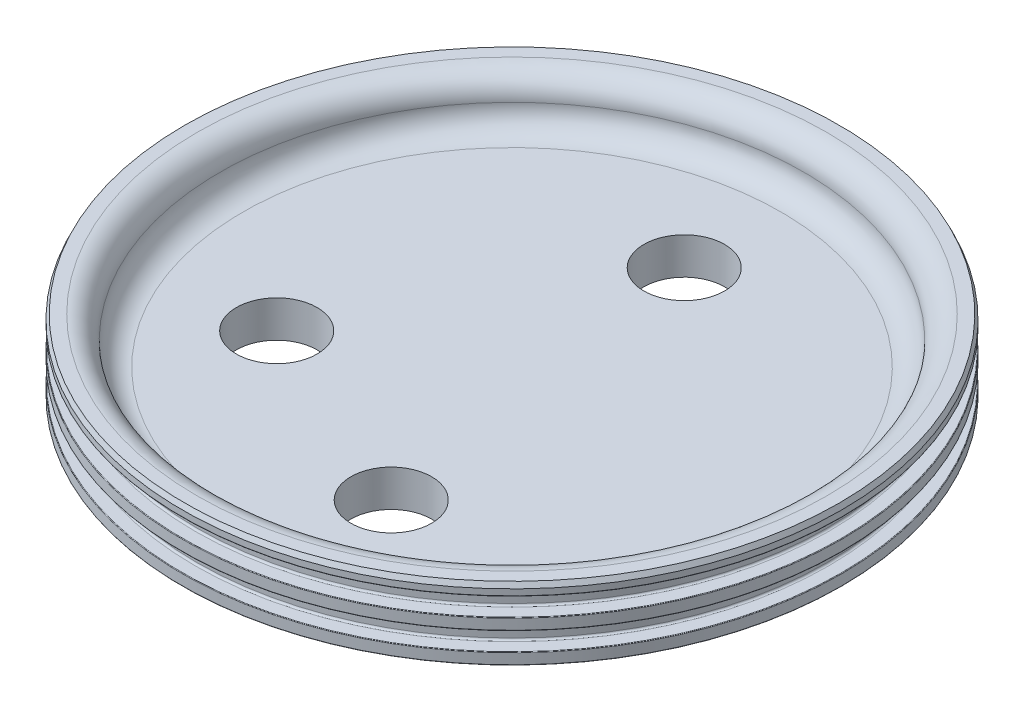
SolidWorks part; units mm, degrees
material "6061-T6 (SS)"
ref_plane "Front Plane" through (0, 0, 0) normal (0, 0, 1) x (1, 0, 0)
ref_plane "Top Plane" through (0, 0, 0) normal (0, 1, 0) x (1, 0, 0)
ref_plane "Right Plane" through (0, 0, 0) normal (1, 0, 0) x (0, 0, -1)
sketch "Sketch1" plane through (0, 0, 0) normal (0, 0, 1) x (1, 0, 0)
  line L0 (0, 48.1922) -> (0, -25.6743) construction
  line L1 (0, 0) -> (72.898, 0)
  line L2 (72.898, 0) -> (72.898, 2.54)
  line L3 (72.898, 2.54) -> (69.6468, 2.54)
  line L4 (69.6468, 2.54) -> (69.6468, 6.604)
  line L5 (69.6468, 6.604) -> (72.898, 6.604)
  line L6 (72.898, 6.604) -> (72.898, 9.144)
  line L7 (72.898, 9.144) -> (69.6468, 9.144)
  line L8 (64.5668, 15.748) -> (64.5668, 5.588)
  line L9 (64.5668, 5.588) -> (0, 5.588)
  line L10 (0, 5.588) -> (0, 0)
  line L11 (69.6468, 9.144) -> (69.6468, 13.208)
  line L12 (69.6468, 13.208) -> (72.898, 13.208)
  line L13 (72.898, 13.208) -> (72.898, 15.748)
  line L14 (72.898, 15.748) -> (64.5668, 15.748)
  dimension "D1" = 145.796
  dimension "D2" = 4.064
  dimension "D5" = 5.588
  dimension "D7" = 4.064
  dimension "D3" = 2.54
  dimension "D4" = 2.54
  dimension "D6" = 69.6468
  dimension "D8" = 5.08
  dimension "D9" = 10.16
revolve "Revolve1" add sketch "Sketch1" angle 360 about L0
sketch "Sketch6" plane through (0, 0, 0) normal (0, -1, 0) x (1, 0, 0)
  circle A0 centre (0, 0) radius 66.04
  dimension "D1" = 132.08
extrude "Boss-Extrude1" add sketch "Sketch6" along normal blind 2.54
fillet "CNC ID Fillet" radius 0.4064 5 edges at (-69.6468, 6.604, 0) (-69.6468, 2.54, 0) (66.04, 0, 0) (-69.6468, 13.208, 0) (-69.6468, 9.144, 0)
fillet "CNC OD Fillet" radius 0.127 6 edges at (-72.898, 6.604, 0) (-72.898, 2.54, 0) (-72.898, 9.144, 0) (-72.898, 13.208, 0) (66.04, -2.54, 0) (-72.898, 0, 0)
chamfer "CNC Chamfers" distance 0.508 angle 65 1 edges at (-72.898, 15.748, 0) first distance on face at (-64.5668, 15.748, 0)
hole_wizard "Pipe Tap Drill for 1/2 Tap - Fill Valve" positions "Sketch13" profile "Sketch14" hole size "1/2" standard "ANSI Inch" end condition through all
sketch "Sketch13" plane through (0, -2.54, 0) normal (0, -1, 0) x (-1, 0, 0)
  point P4 (0, 38.1)
  dimension "D1" = 38.1
sketch "Sketch14" plane through (0, -2.54, -38.1) normal (1, 0, 0) x (0, 0, -1)
  line L0 (0, 0) -> (0, 18.288)
  line L1 (0, 18.288) -> (8.9281, 18.288)
  line L2 (8.9281, 18.288) -> (8.9281, 0)
  line L5 (8.9281, 0) -> (0, 0)
  line L11 (0, -6.35) -> (0, 107.95) construction
  dimension "Thru Hole Dia." = 17.8562
  dimension "Thru Hole Depth" = 18.288
hole_wizard "Pipe Tap Drill for 1/4 Tap - Solenoid Valve" positions "Sketch15" profile "Sketch16" hole size "1/2" standard "ANSI Inch" end condition through all
sketch "Sketch15" plane through (0, -2.54, 0) normal (0, -1, 0) x (-1, 0, 0)
  line L2 (-12.0892, -38.8003) -> (0, 0) construction
  line L3 (0, 0) -> (0, -38.8003) construction
  point P4 (-12.0892, -38.8003)
  dimension "D1" = 17.306
  dimension "D2" = 40.64
  dimension "D3" = 38.8003
sketch "Sketch16" plane through (12.0892, -2.54, 38.8003) normal (1, 0, 0) x (0, 0, -1)
  line L0 (0, 0) -> (0, 18.288)
  line L1 (0, 18.288) -> (8.9281, 18.288)
  line L2 (8.9281, 18.288) -> (8.9281, 0)
  line L5 (8.9281, 0) -> (0, 0)
  line L11 (0, -6.35) -> (0, 107.95) construction
  dimension "Thru Hole Dia." = 17.8562
  dimension "Thru Hole Depth" = 18.288
hole_wizard "Pipe Tap Drill for 1/2 Tap - Cryo Valve" positions "Sketch17" profile "Sketch18" hole size "1/2" standard "ANSI Inch" end condition through all
sketch "Sketch17" plane through (0, -2.54, 0) normal (0, -1, 0) x (-1, 0, 0)
  line L0 (32.9956, -19.05) -> (17.2813, -19.05) construction
  line L2 (32.9956, -19.05) -> (0, 0) construction
  point P4 (32.9956, -19.05)
  dimension "D1" = 30
  dimension "D2" = 38.1
sketch "Sketch18" plane through (-32.9956, -2.54, 19.05) normal (1, 0, 0) x (0, 0, -1)
  line L0 (0, 0) -> (0, 18.288)
  line L1 (0, 18.288) -> (8.9281, 18.288)
  line L2 (8.9281, 18.288) -> (8.9281, 0)
  line L5 (8.9281, 0) -> (0, 0)
  line L11 (0, -6.35) -> (0, 107.95) construction
  dimension "Thru Hole Dia." = 17.8562
  dimension "Thru Hole Depth" = 18.288
fillet "Fillet1" radius 5.08 2 edges at (-64.5668, 5.588, 0) (-64.5668, 15.748, 0)
equation "\"D6@Sketch1\"=5.484/2"
